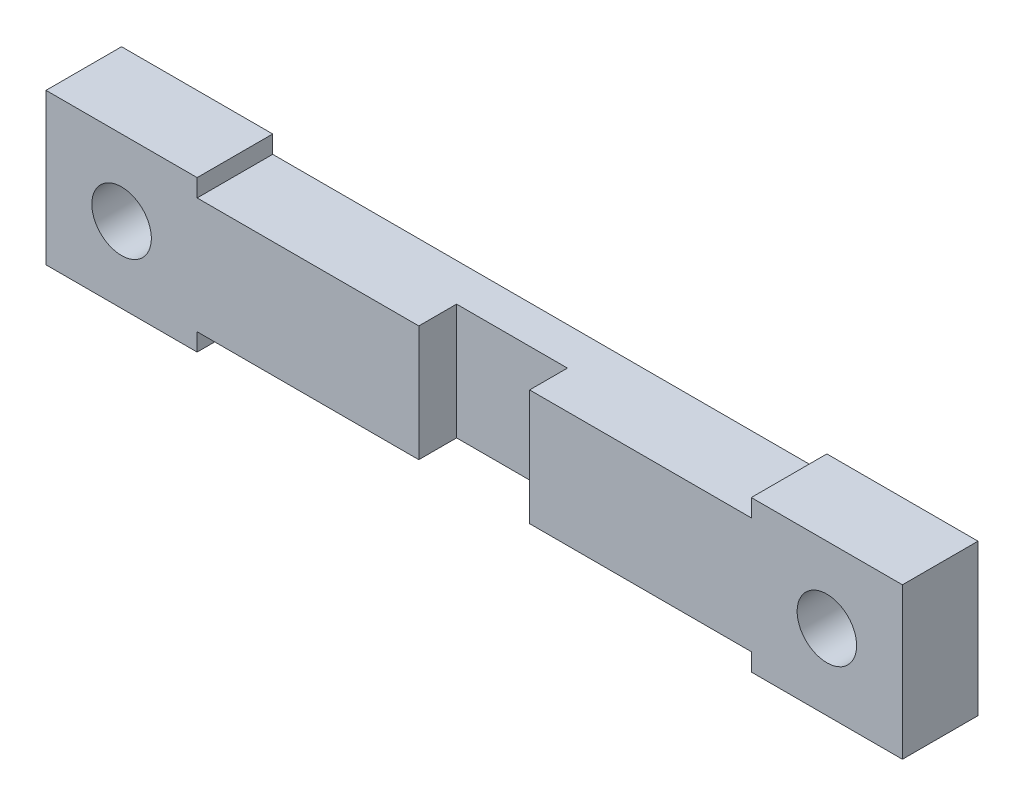
SolidWorks part; units mm, degrees
ref_plane "Front Plane" through (0, 0, 0) normal (0, 0, 1) x (1, 0, 0)
ref_plane "Top Plane" through (0, 0, 0) normal (0, 1, 0) x (1, 0, 0)
ref_plane "Right Plane" through (0, 0, 0) normal (1, 0, 0) x (0, 0, -1)
sketch "Sketch1" plane through (0, 0, 0) normal (0, 0, 1) x (1, 0, 0)
  line L0 (0, 2.921) -> (0, -2.921) construction
  line L1 (-13.97, -2.921) -> (13.97, -2.921)
  line L2 (-13.97, -2.921) -> (-13.97, 2.921)
  line L3 (-13.97, 2.921) -> (13.97, 2.921)
  line L4 (13.97, -2.921) -> (13.97, 2.921)
  line L5 (-13.97, -2.921) -> (13.97, 2.921) construction
  line L6 (-13.97, 2.921) -> (13.97, -2.921) construction
  line L7 (21.59, 0) -> (13.97, 0) construction
  line L8 (13.97, 3.81) -> (21.59, 3.81)
  line L9 (13.97, 3.81) -> (13.97, -3.81)
  line L10 (13.97, -3.81) -> (21.59, -3.81)
  line L11 (21.59, 3.81) -> (21.59, -3.81)
  line L12 (-13.97, -3.81) -> (-21.59, -3.81)
  line L13 (-21.59, 3.81) -> (-21.59, -3.81)
  line L14 (-13.97, 3.81) -> (-21.59, 3.81)
  line L15 (-13.97, 3.81) -> (-13.97, -3.81)
  circle A0 centre (17.78, 0) radius 1.5
  circle A1 centre (-17.78, 0) radius 1.5
  circle A2 centre (0, 0) radius 17.78 construction
  point P0 (0, 0)
  dimension "D1" = 3
  dimension "D2" = 35.56
  dimension "D3" = 3.81
  dimension "D4" = 3.81
  dimension "D5" = 5.842
extrude "Boss-Extrude1" add sketch "Sketch1" along normal blind 3.81 contours L15 L14 L13 L12 L2 A1 | L1 L4 L3 L2 | L11 L8 L9 L4 L10 A0 region at (0, 0, 0) region at (-14.0778, -3.3655, 0) region at (14.0778, 0, 0)
sketch "Sketch2" plane through (0, 0, 3.81) normal (0, 0, 1) x (1, 0, 0)
  line L0 (-13.97, 2.921) -> (13.97, 2.921) construction
  line L1 (-2.794, -2.921) -> (2.794, -2.921)
  line L2 (-2.794, -2.921) -> (-2.794, 2.921)
  line L3 (-2.794, 2.921) -> (2.794, 2.921)
  line L4 (2.794, -2.921) -> (2.794, 2.921)
  line L5 (-2.794, -2.921) -> (2.794, 2.921) construction
  line L6 (-2.794, 2.921) -> (2.794, -2.921) construction
  point P0 (0, 0)
  dimension "D1" = 5.588
extrude "Cut-Extrude1" cut sketch "Sketch2" against normal blind 1.905
